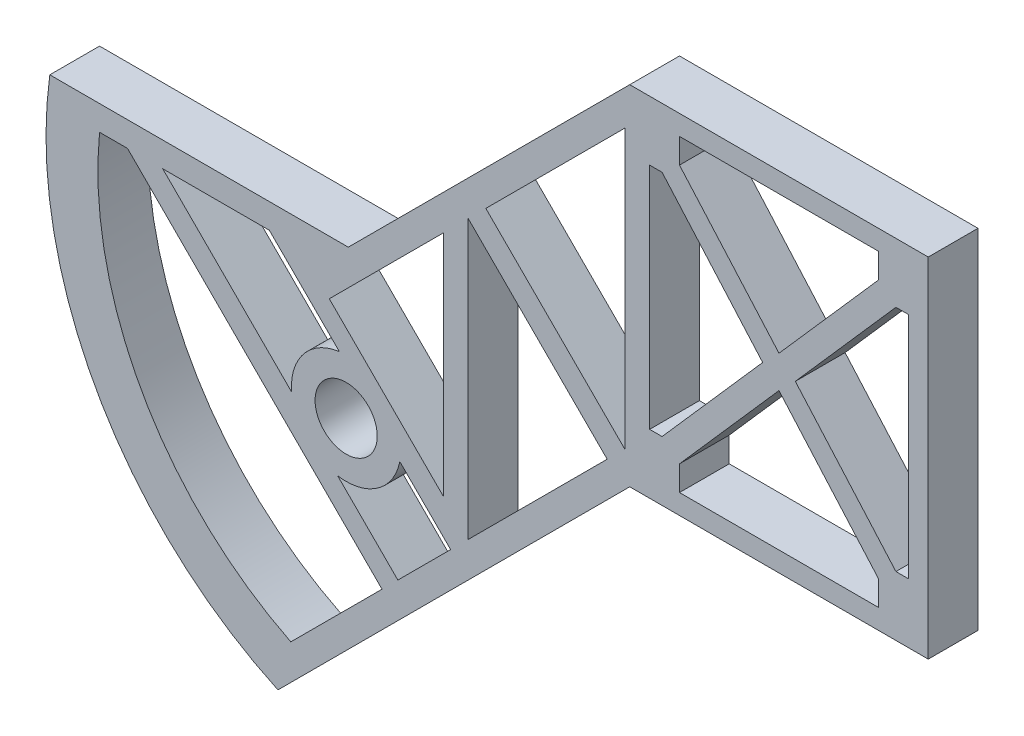
SolidWorks part; units mm, degrees
material "Magnesium Alloy"
ref_plane "Front Plane" through (0, 0, 0) normal (0, 0, 1) x (1, 0, 0)
ref_plane "Top Plane" through (0, 0, 0) normal (0, 1, 0) x (1, 0, 0)
ref_plane "Right Plane" through (0, 0, 0) normal (1, 0, 0) x (0, 0, -1)
sketch "Sketch1" plane through (0, 0, 0) normal (0, 0, 1) x (1, 0, 0)
  line L0 (29.6783, 155.2055) -> (-42.1637, 83.3634)
  line L1 (29.6783, 155.2055) -> (105.8783, 155.2055)
  line L3 (29.6783, 66.3055) -> (105.8783, 66.3055)
  line L4 (105.8783, 155.2055) -> (105.8783, 66.3055)
  line L5 (29.6783, 66.3055) -> (-60.1242, -23.4971)
  line L6 (-42.1637, 83.3634) -> (-118.3637, 83.3634)
  line L7 (67.7783, 154.5471) -> (67.7783, 66.3055) construction
  line L8 (191.9818, 110.7555) -> (-10.1946, 110.7555) construction
  arc A1 (-118.3637, 83.3634) -> (-60.1242, -23.4971) centre (-16.9914, 69.3112) ccw
  dimension "D1" = 88.9
  dimension "D2" = 76.2
  dimension "D3" = 127
  dimension "D4" = 101.6
  dimension "D5" = 135
  dimension "D6" = 76.2
  dimension "D7" = 44.45
  dimension "D8" = 38.1
  dimension "D9" = 76.2
  dimension "D11" = 135
extrude "Boss-Extrude1" add sketch "Sketch1" along normal blind 12.7
sketch "Sketch2" plane through (0, 0, 12.7) normal (0, 0, 1) x (1, 0, 0)
  line L0 (-42.1637, 83.3634) -> (-118.3637, 83.3634) construction
  line L1 (105.8783, 66.3055) -> (105.8783, 155.2055) construction
  circle A0 centre (-42.7117, 45.2634) radius 7.9375
  dimension "D2" = 15.875
  dimension "D1" = 38.1
  dimension "D3" = 148.59
extrude "Cut-Extrude1" cut sketch "Sketch2" against normal blind 25.4
sketch "Sketch3" plane through (0, 0, 12.7) normal (0, 0, 1) x (1, 0, 0)
  line L1 (93.1783, 143.7755) -> (67.7783, 114.8802)
  line L2 (67.7783, 114.8802) -> (42.3783, 143.7755)
  line L3 (97.6233, 139.9655) -> (71.9467, 110.7555)
  line L4 (71.9467, 110.7555) -> (97.6233, 81.5455)
  line L6 (105.8783, 66.3055) -> (105.8783, 155.2055) construction
  line L7 (105.8783, 155.2055) -> (29.6783, 155.2055) construction
  line L8 (29.6783, 155.2055) -> (29.6783, 66.3055) construction
  line L9 (-60.1242, -23.4971) -> (29.6783, 66.3055) construction
  line L10 (29.6783, 66.3055) -> (105.8783, 66.3055) construction
  line L11 (42.3783, 143.7755) -> (42.3783, 150.1255)
  line L12 (42.3783, 150.1255) -> (93.1783, 150.1255)
  line L13 (93.1783, 150.1255) -> (93.1783, 143.7755)
  line L14 (97.6233, 139.9655) -> (100.7983, 139.9655)
  line L15 (100.7983, 139.9655) -> (100.7983, 81.5455)
  line L16 (100.7983, 81.5455) -> (97.6233, 81.5455)
  line L17 (34.7583, 139.9655) -> (37.9333, 139.9655)
  line L18 (37.9333, 139.9655) -> (63.61, 110.7555)
  line L19 (63.61, 110.7555) -> (37.9333, 81.5455)
  line L20 (37.9333, 81.5455) -> (34.7583, 81.5455)
  line L21 (34.7583, 81.5455) -> (34.7583, 139.9655)
  line L22 (42.3783, 71.3855) -> (42.3783, 77.7355)
  line L23 (42.3783, 77.7355) -> (67.7783, 106.6308)
  line L24 (67.7783, 106.6308) -> (93.1783, 77.7355)
  line L25 (93.1783, 77.7355) -> (93.1783, 71.3855)
  line L26 (93.1783, 71.3855) -> (42.3783, 71.3855)
  point P17 (42.3783, 74.5605)
  dimension "D1" = 38.1
  dimension "D2" = 6.35
  dimension "D3" = 12.7
  dimension "D4" = 15.24
  dimension "D5" = 5.08
  dimension "D6" = 12.7
  dimension "D7" = 15.24
  dimension "D8" = 3.175
  dimension "D9" = 5.08
  dimension "D10" = 44.45
  dimension "D11" = 5.08
  dimension "D12" = 5.08
  dimension "D13" = 12.7
  dimension "D14" = 12.7
  dimension "D15" = 15.24
extrude "Cut-Extrude2" cut sketch "Sketch3" against normal blind 25.4
sketch "Sketch4" plane through (0, 0, 12.7) normal (0, 0, 1) x (1, 0, 0)
  line L0 (-7.0614, 109.4855) -> (28.4083, 74.0158)
  line L1 (28.4083, 74.0158) -> (28.4083, 144.9552)
  line L2 (28.4083, 144.9552) -> (-7.0614, 109.4855)
  line L3 (29.6783, 155.2055) -> (-42.1637, 83.3634) construction
  line L4 (-60.1242, -23.4971) -> (29.6783, 66.3055) construction
  line L5 (34.7583, 139.9655) -> (34.7583, 81.5455) construction
  line L6 (23.9182, 69.5256) -> (-11.5515, 34.0559)
  line L7 (-11.5515, 34.0559) -> (-11.5515, 104.9954)
  line L8 (-11.5515, 104.9954) -> (23.9182, 69.5256)
  line L9 (-17.9015, 98.6454) -> (-47.0213, 69.5256)
  line L10 (-47.0213, 69.5256) -> (-17.9015, 40.4059)
  line L11 (-17.9015, 40.4059) -> (-17.9015, 98.6454)
  point P15 (0, 0)
  point P16 (-16.7198, 28.8876)
  point P17 (-16.904, 28.7034)
  point P18 (0, 0)
  point P19 (-16.6277, 28.9797)
  point P20 (-17.0497, 40.0606)
  dimension "D1" = 6.35
  dimension "D2" = 6.35
  dimension "D3" = 6.35
  dimension "D4" = 6.35
  dimension "D5" = 6.35
  dimension "D6" = 6.35
  dimension "D7" = 6.35
  dimension "D8" = 6.35
  dimension "D9" = 0
extrude "Cut-Extrude3" cut sketch "Sketch4" against normal blind 25.4
ref_axis "Axis1" through (-42.7117, 45.2634, 0) along (0, 0, 1)
sketch "Sketch5" plane through (0, 0, 12.7) normal (0, 0, 1) x (1, 0, 0)
  line L4 (-47.0213, 69.5256) -> (-17.9015, 40.4059) construction
  line L6 (-29.0107, 42.5348) -> (-16.0417, 29.5658)
  line L7 (-16.0417, 29.5658) -> (-29.5121, 16.0954)
  line L8 (-29.5121, 16.0954) -> (-44.8793, 31.4626)
  line L9 (-60.1242, -23.4971) -> (29.6783, 66.3055) construction
  line L10 (-44.434, 59.1269) -> (-62.3206, 77.0134)
  line L11 (-62.3206, 77.0134) -> (-89.5394, 77.0134)
  line L12 (-89.5394, 77.0134) -> (-56.6338, 44.1078)
  line L13 (-42.1637, 83.3634) -> (-118.3637, 83.3634) construction
  arc A0 (-29.0107, 42.5348) -> (-44.8793, 31.4626) centre (-42.7117, 45.2634) cw
  arc A1 (-44.434, 59.1269) -> (-56.6338, 44.1078) centre (-42.7117, 45.2634) ccw
  point P4 (0, 0)
  dimension "D1" = 6.35
  dimension "D6" = 13.97
  dimension "D2" = 6.35
  dimension "D7" = 6.35
  dimension "D8" = 19.05
extrude "Cut-Extrude4" cut sketch "Sketch5" against normal blind 25.4
sketch "Sketch6" plane through (0, 0, 12.7) normal (0, 0, 1) x (1, 0, 0)
  line L5 (-56.8372, -11.2298) -> (-33.5568, 12.0506)
  line L10 (-33.5568, 12.0506) -> (-98.5196, 77.0134)
  line L11 (-98.5196, 77.0134) -> (-105.6637, 77.0134)
  line L12 (-42.1637, 83.3634) -> (-118.3637, 83.3634) construction
  line L13 (-89.5394, 77.0134) -> (-56.6338, 44.1078) construction
  arc A1 (-56.8372, -11.2298) -> (-105.6637, 77.0134) centre (-17.188, 68.3387) cw
  dimension "D5" = 88.9
  dimension "D1" = 6.35
  dimension "D2" = 6.35
  dimension "D3" = 12.7
  dimension "D4" = 12.7
extrude "Cut-Extrude5" cut sketch "Sketch6" against normal blind 25.4
